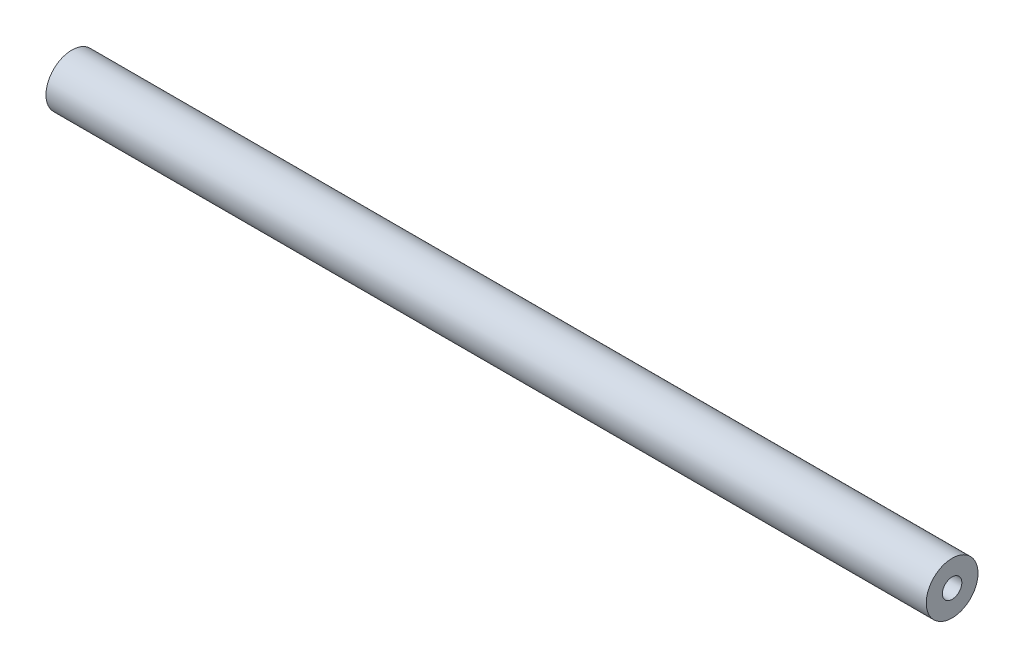
SolidWorks part; units mm, degrees
material "6061 合金"
ref_plane "前视基准面" through (0, 0, 0) normal (0, 0, 1) x (1, 0, 0)
ref_plane "上视基准面" through (0, 0, 0) normal (0, 1, 0) x (1, 0, 0)
ref_plane "右视基准面" through (0, 0, 0) normal (1, 0, 0) x (0, 0, -1)
sketch "草图1" plane through (0, 0, 0) normal (0, 0, 1) x (1, 0, 0)
  line L1 (0, 0) -> (136, 0)
  line L2 (0, 0) -> (0, -8)
  line L3 (0, -8) -> (136, -8)
  line L4 (136, 0) -> (136, -8)
  dimension "D1" = 136
  dimension "D2" = 8
extrude "凸台-拉伸1" add sketch "草图1" along normal blind 8
sketch "草图2" plane through (0, 0, 0) normal (-1, 0, 0) x (0, 0, 1)
  line L0 (0, -4) -> (8, -4) construction
  line L1 (0, 0) -> (0, -8) construction
  line L2 (8, 0) -> (8, -8) construction
  line L3 (4, -8) -> (4, 0) construction
  line L4 (8, -8) -> (0, -8) construction
  line L5 (8, 0) -> (0, 0) construction
  circle A0 centre (4, -4) radius 1.5
  dimension "D1" = 3
extrude "切除-拉伸1" cut sketch "草图2" against normal blind 10
cosmetic thread "装饰螺纹线1" parameters "D2"=4
extrude "切除-拉伸2" cut sketch "草图2<2>" along normal blind 10 from offset 136 offset against normal yes
sketch "草图2<2>" plane through (0, 0, 0) normal (-1, 0, 0) x (0, 0, 1) same geometry as "草图2"
cosmetic thread "装饰螺纹线2" parameters "D2"=4
sketch "草图3" plane through (136, 0, 0) normal (1, 0, 0) x (0, 0, -1)
  circle A0 centre (-4, -4) radius 4
  circle A1 centre (-4, -4) radius 6
  dimension "D1" = 12
  dimension "D2" = 8
extrude "切除-拉伸3" cut sketch "草图3" against normal through all
